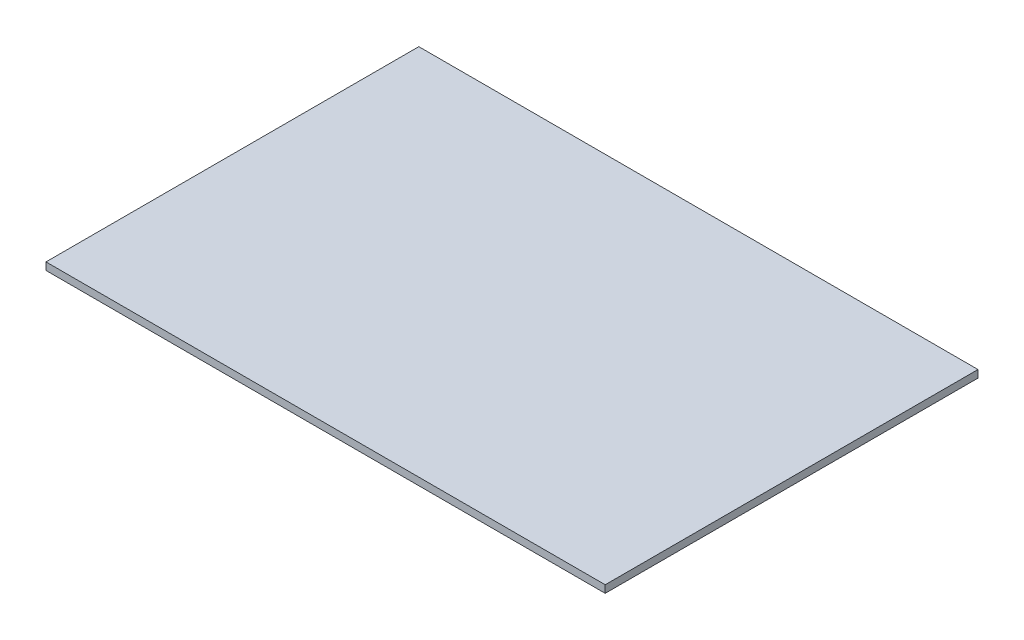
SolidWorks part; units mm, degrees
ref_plane "Front Plane" through (0, 0, 0) normal (0, 0, 1) x (1, 0, 0)
ref_plane "Top Plane" through (0, 0, 0) normal (0, 1, 0) x (1, 0, 0)
ref_plane "Right Plane" through (0, 0, 0) normal (1, 0, 0) x (0, 0, -1)
sketch "Sketch1" plane through (0, 0, 0) normal (0, 1, 0) x (1, 0, 0)
  line L1 (100, 5.3239) -> (400, 5.3239)
  line L2 (100, 5.3239) -> (100, 205.3239)
  line L3 (100, 205.3239) -> (400, 205.3239)
  line L4 (400, 5.3239) -> (400, 205.3239)
  dimension "D1" = 300
  dimension "D2" = 200
extrude "Boss-Extrude1" add sketch "Sketch1" along normal blind 4
